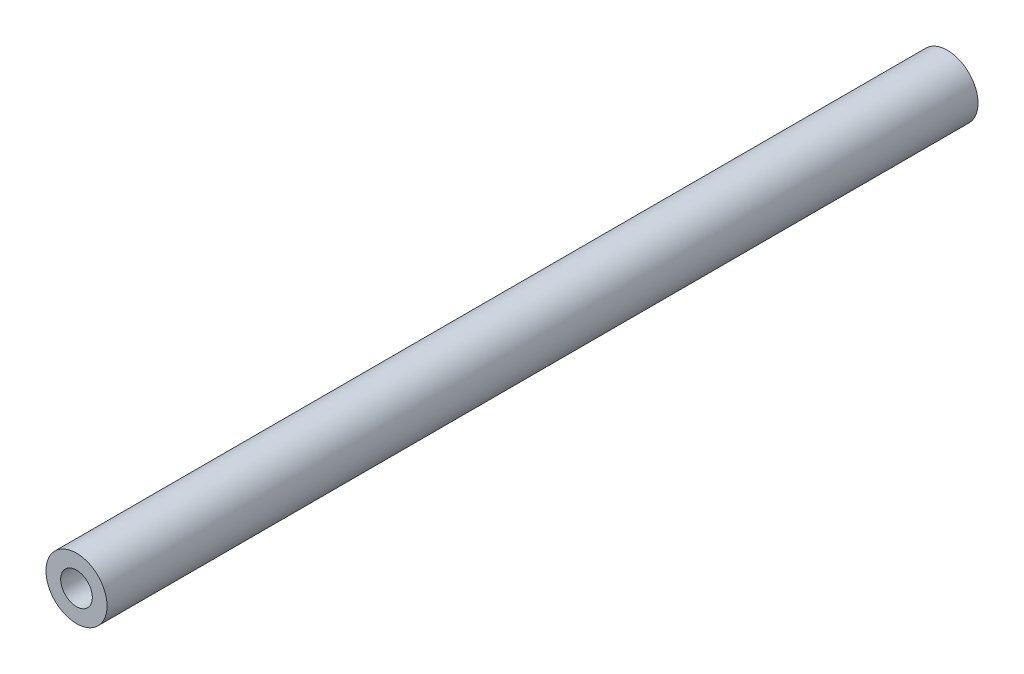
SolidWorks part; units mm, degrees
material "Plain Carbon Steel"
ref_plane "Front Plane" through (0, 0, 0) normal (0, 0, 1) x (1, 0, 0)
ref_plane "Top Plane" through (0, 0, 0) normal (0, 1, 0) x (1, 0, 0)
ref_plane "Right Plane" through (0, 0, 0) normal (1, 0, 0) x (0, 0, -1)
sketch "Sketch1" plane through (0, 0, 0) normal (0, 0, 1) x (1, 0, 0)
  circle A0 centre (0, 0) radius 5
  dimension "D1" = 10
extrude "Boss-Extrude1" add sketch "Sketch1" along normal blind 142.53
hole_wizard "#6 (0.204) Diameter Hole1" positions "Sketch2" profile "Sketch3" hole size "#6" standard "ANSI Inch"
sketch "Sketch2" plane through (0, 0, 0) normal (0, 0, -1) x (-1, 0, 0)
  point P0 (0, 0)
sketch "Sketch3" plane through (0, 0, 0) normal (1, 0, 0) x (0, 1, 0)
  line L0 (0, 0) -> (0, 31.5567)
  line L1 (0, 31.5567) -> (2.5908, 30)
  line L2 (2.5908, 30) -> (2.5908, 0)
  line L5 (2.5908, 0) -> (0, 0)
  line L10 (0, 31.5567) -> (-2.5908, 30) construction
  line L11 (0, -6.35) -> (0, 107.95) construction
  dimension "Hole Dia." = 5.1816
  dimension "Hole Depth" = 30
  dimension "Drill Angle" = 118
hole_wizard "#6 (0.204) Diameter Hole2" positions "Sketch4" profile "Sketch5" hole size "#6" standard "ANSI Inch"
sketch "Sketch4" plane through (0, 0, 142.53) normal (0, 0, 1) x (1, 0, 0)
  point P0 (0, 0)
sketch "Sketch5" plane through (0, 0, 142.53) normal (1, 0, 0) x (0, -1, 0)
  line L0 (0, 0) -> (0, 31.5567)
  line L1 (0, 31.5567) -> (2.5908, 30)
  line L2 (2.5908, 30) -> (2.5908, 0)
  line L5 (2.5908, 0) -> (0, 0)
  line L10 (0, 31.5567) -> (-2.5908, 30) construction
  line L11 (0, -6.35) -> (0, 107.95) construction
  dimension "Hole Dia." = 5.1816
  dimension "Hole Depth" = 30
  dimension "Drill Angle" = 118
